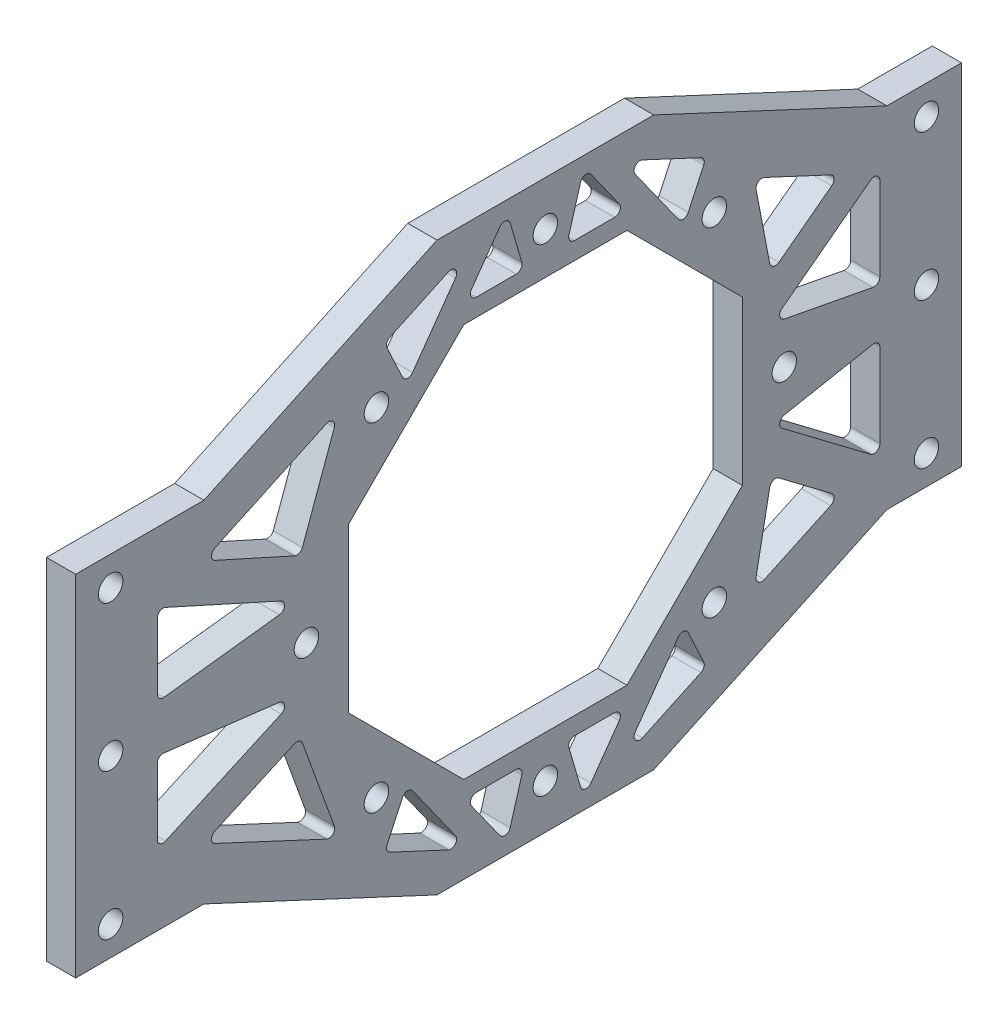
SolidWorks part; units mm, degrees
material "玻纤"
ref_plane "前视基准面" through (0, 0, 0) normal (0, 0, 1) x (1, 0, 0)
ref_plane "上视基准面" through (0, 0, 0) normal (0, 1, 0) x (1, 0, 0)
ref_plane "右视基准面" through (0, 0, 0) normal (1, 0, 0) x (0, 0, -1)
sketch "草图1" plane through (0, 0, 0) normal (1, 0, 0) x (0, 0, -1)
  line L0 (-74.6, 30) -> (-74.6, -30) construction
  line L1 (-78.6, -30) -> (78.6, -30)
  line L2 (-78.6, -30) -> (-78.6, 30)
  line L3 (-78.6, 30) -> (78.6, 30)
  line L4 (78.6, -30) -> (78.6, 30)
  line L5 (-78.6, -30) -> (78.6, 30) construction
  line L6 (-78.6, 30) -> (78.6, -30) construction
  line L7 (0, 0) -> (0, -30) construction
  line L8 (65.4, 30) -> (65.4, -30) construction
  line L9 (78.6, -30) -> (78.6, 30)
  circle A0 centre (-74.6, 0) radius 2.1
  circle A1 centre (-74.6, 25) radius 2.1
  circle A3 centre (-74.6, -25) radius 2.1
  circle A4 centre (65.4, -25) radius 2.1
  circle A6 centre (65.4, 25) radius 2.1
  circle A7 centre (65.4, 0) radius 2.1
  point P0 (0, 0)
  point P15 (-74.6, 0)
  dimension "D4" = 4.2
  dimension "D8" = 5
  dimension "D10" = 5
  dimension "D13" = 4.2
  dimension "D1" = 60
  dimension "D2" = 157.2
  dimension "D3" = 4
  dimension "D12" = 65.4
extrude "凸台-拉伸1" add sketch "草图1" along normal blind 5 contours L1 L4 L3 L2 A6 A4 A3 A1 A0 A7 region at (0, 0, -0.0409)
sketch "草图2" plane through (5, 0, 0) normal (1, 0, 0) x (0, 0, -1)
  line L0 (-58.6, 30) -> (-58.6, -30)
  line L1 (-78.6, 30) -> (78.6, 30) construction
  line L2 (-78.6, -30) -> (78.6, -30) construction
  line L3 (-58.6, -30) -> (-18.6, -48.6523)
  line L4 (-18.6, -48.6523) -> (18.6, -48.6523)
  line L5 (0, -48.6523) -> (0, 0)
  line L6 (-78.6, -30) -> (-78.6, 30) construction
  line L7 (58.6, -30) -> (18.6, -48.6523)
  line L8 (58.6, 30) -> (58.6, -30)
  line L9 (-58.6, 0) -> (58.6, 0) construction
  line L10 (58.6, 30) -> (18.6, 48.6523)
  line L11 (-18.6, 48.6523) -> (18.6, 48.6523)
  line L12 (-58.6, 30) -> (-18.6, 48.6523)
  circle A0 centre (0, 0) radius 41 construction
  circle A1 centre (-41, 0) radius 2.1
  circle A2 centre (-28.9914, 28.9914) radius 2.1
  circle A3 centre (0, 41) radius 2.1
  circle A4 centre (28.9914, 28.9914) radius 2.1
  circle A5 centre (41, 0) radius 2.1
  circle A6 centre (28.9914, -28.9914) radius 2.1
  circle A7 centre (0, -41) radius 2.1
  circle A8 centre (-28.9914, -28.9914) radius 2.1
  line M13 (-78.6, -30) -> (78.6, -30)
  line M15 (78.6, 30) -> (-78.6, 30)
  dimension "D1" = 82
  dimension "D5" = 4.2
  dimension "D2" = 20
  dimension "D3" = 25
  dimension "D4" = 40
  dimension "D6" = 8
extrude "凸台-拉伸2" add sketch "草图2" against normal blind 5 contours A4 L10 L11 L12 A2 A3 M15 | A8 L3 L4 L5 A7 M13 | A7 L5 L4 L7 A6 M13 region at (5, 37.7126, 0) region at (5, -37.7126, 21.1914) region at (5, -37.7126, -21.1914)
extrude "切除-拉伸1" cut sketch "草图2<3>" against normal blind 5 contours A2 M15 | A8 M13 | A6 M13 | A5 | A4 M15 | A1 region at (5, 28.6125, 28.9914) region at (5, -28.6125, 28.9914) region at (5, 28.6125, -28.9914) region at (5, -28.6125, -28.9914) region at (5, 0, -41)
sketch "草图2<3>" plane through (5, 0, 0) normal (1, 0, 0) x (0, 0, -1) same geometry as "草图2"
sketch "草图3" plane through (0, 0, 0) normal (-1, 0, 0) x (0, 0, 1)
  line L7 (-14, 33.799) -> (-33.799, 14)
  line L8 (-33.799, 14) -> (-33.799, -14)
  line L9 (-33.799, -14) -> (-14, -33.799)
  line L10 (-14, -33.799) -> (14, -33.799)
  line L11 (14, -33.799) -> (33.799, -14)
  line L12 (33.799, -14) -> (33.799, 14)
  line L13 (33.799, 14) -> (14, 33.799)
  line L14 (14, 33.799) -> (-14, 33.799)
  circle A0 centre (0, 0) radius 33.799 construction
  dimension "D1" = 28
extrude "切除-拉伸2" cut sketch "草图3" against normal blind 5
sketch "草图4" plane through (0, 0, 0) normal (-1, 0, 0) x (0, 0, 1)
  line L0 (-58.6, -30) -> (-78.6, -30) construction
  line L1 (-78.6, 30) -> (-71.4, 30)
  line L2 (-78.6, 30) -> (-78.6, -30)
  line L3 (-78.6, -30) -> (-71.4, -30)
  line L4 (-71.4, 30) -> (-71.4, -30)
  line L5 (-48.9578, 24.5658) -> (-37.5643, 29.8787)
  line L6 (-36.1597, 28.7835) -> (-38.4959, 16.6375)
  line L7 (-40.0801, 16.0281) -> (-49.1375, 22.8612)
  line L8 (-55.7977, 20.3699) -> (-40.5994, 8.9039)
  line L9 (-41.0145, 7.1233) -> (-56.2128, 4.2263)
  line L10 (-57.4, 5.2086) -> (-57.4, 19.5716)
  line L11 (-58.6, 30) -> (-18.6, 48.6523) construction
  line L12 (-33.799, 14) -> (-33.799, -14) construction
  line L16 (-11.8725, 36.799) -> (-5, 36.799)
  line L17 (-16.643, 42.9446) -> (-26.6924, 38.2585)
  line L18 (-27.1761, 36.9296) -> (-24.5153, 31.2234)
  line L19 (-22.794, 31.0665) -> (-15.4053, 41.4589)
  line L27 (-14, 33.799) -> (-33.799, 14) construction
  line L32 (-12.6875, 38.3784) -> (-7.815, 45.2318)
  line L33 (-6.04, 44.9325) -> (-4.04, 38.0791)
  line L34 (18.6, 48.6523) -> (-18.6, 48.6523) construction
  line L35 (14, 33.799) -> (-14, 33.799) construction
  line L36 (0, 33.799) -> (0, -33.799) construction
  line L37 (-14, -33.799) -> (14, -33.799) construction
  line L38 (-33.799, 0) -> (33.799, 0) construction
  line L39 (33.799, -14) -> (33.799, 14) construction
  line L40 (-12.6875, -38.3784) -> (-7.815, -45.2318)
  line L41 (-11.8725, -36.799) -> (-5, -36.799)
  line L42 (-6.04, -44.9325) -> (-4.04, -38.0791)
  line L43 (-27.1761, -36.9296) -> (-24.5153, -31.2234)
  line L44 (-16.643, -42.9446) -> (-26.6924, -38.2585)
  line L45 (-22.794, -31.0665) -> (-15.4053, -41.4589)
  line L46 (-36.1597, -28.7835) -> (-38.4959, -16.6375)
  line L47 (-48.9578, -24.5658) -> (-37.5643, -29.8787)
  line L48 (-40.0801, -16.0281) -> (-49.1375, -22.8612)
  line L49 (-41.0145, -7.1233) -> (-56.2128, -4.2263)
  line L50 (-55.7977, -20.3699) -> (-40.5994, -8.9039)
  line L51 (-57.4, -5.2086) -> (-57.4, -19.5716)
  line L52 (11.8725, -36.799) -> (5, -36.799)
  line L53 (6.04, -44.9325) -> (4.04, -38.0791)
  line L54 (12.6875, -38.3784) -> (7.815, -45.2318)
  line L55 (16.643, -42.9446) -> (26.6924, -38.2585)
  line L56 (22.794, -31.0665) -> (15.4053, -41.4589)
  line L57 (27.1761, -36.9296) -> (24.5153, -31.2234)
  line L64 (12.6875, 38.3784) -> (7.815, 45.2318)
  line L65 (11.8725, 36.799) -> (5, 36.799)
  line L66 (6.04, 44.9325) -> (4.04, 38.0791)
  line L67 (27.1761, 36.9296) -> (24.5153, 31.2234)
  line L68 (16.643, 42.9446) -> (26.6924, 38.2585)
  line L69 (22.794, 31.0665) -> (15.4053, 41.4589)
  line L76 (37.5709, 30.873) -> (56.7287, 21.9396)
  line L77 (56.7175, 20.1219) -> (43.0449, 13.9499)
  line L78 (41.6935, 14.52) -> (36.2084, 29.6254)
  line L79 (45.3384, 8.4022) -> (65.1886, 17.3629)
  line L80 (66.6, 16.4514) -> (66.6, 5.1262)
  line L81 (65.4817, 4.1332) -> (45.6316, 6.4978)
  line L82 (58.6, 30) -> (18.6, 48.6523) construction
  line L83 (78.6, 30) -> (58.6, 30) construction
  line L84 (66.6, -16.4514) -> (66.6, -5.1262)
  line L85 (45.3384, -8.4022) -> (65.1886, -17.3629)
  line L86 (65.4817, -4.1332) -> (45.6316, -6.4978)
  line L87 (56.7175, -20.1219) -> (43.0449, -13.9499)
  line L88 (37.5709, -30.873) -> (56.7287, -21.9396)
  line L89 (41.6935, -14.52) -> (36.2084, -29.6254)
  circle A0 centre (-65.4, 25) radius 2.1 construction
  circle A2 centre (-41, 0) radius 2.1 construction
  circle A3 centre (-28.9914, 28.9914) radius 2.1 construction
  circle A4 centre (-65.4, 0) radius 2.1 construction
  arc A5 (-55.7977, 20.3699) -> (-57.4, 19.5716) centre (-56.4, 19.5716) ccw
  arc A6 (-56.2128, 4.2263) -> (-57.4, 5.2086) centre (-56.4, 5.2086) cw
  arc A7 (-40.5994, 8.9039) -> (-41.0145, 7.1233) centre (-41.2017, 8.1056) cw
  arc A8 (-37.5643, 29.8787) -> (-36.1597, 28.7835) centre (-37.1417, 28.9724) cw
  arc A9 (-38.4959, 16.6375) -> (-40.0801, 16.0281) centre (-39.4779, 16.8264) cw
  arc A10 (-48.9578, 24.5658) -> (-49.1375, 22.8612) centre (-48.5352, 23.6595) ccw
  arc A17 (-16.643, 42.9446) -> (-15.4053, 41.4589) centre (-16.2203, 42.0383) cw
  arc A18 (-24.5153, 31.2234) -> (-22.794, 31.0665) centre (-23.609, 31.646) ccw
  arc A19 (-26.6924, 38.2585) -> (-27.1761, 36.9296) centre (-26.2698, 37.3522) ccw
  arc A20 (-5, 36.799) -> (-4.04, 38.0791) centre (-5, 37.799) ccw
  arc A21 (-11.8725, 36.799) -> (-12.6875, 38.3784) centre (-11.8725, 37.799) cw
  arc A22 (-7.815, 45.2318) -> (-6.04, 44.9325) centre (-7, 44.6523) cw
  circle A23 centre (0, 41) radius 2.1 construction
  arc A24 (-11.8725, -36.799) -> (-12.6875, -38.3784) centre (-11.8725, -37.799) ccw
  arc A25 (-5, -36.799) -> (-4.04, -38.0791) centre (-5, -37.799) cw
  arc A26 (-7.815, -45.2318) -> (-6.04, -44.9325) centre (-7, -44.6523) ccw
  arc A27 (-26.6924, -38.2585) -> (-27.1761, -36.9296) centre (-26.2698, -37.3522) cw
  arc A28 (-16.643, -42.9446) -> (-15.4053, -41.4589) centre (-16.2203, -42.0383) ccw
  arc A29 (-24.5153, -31.2234) -> (-22.794, -31.0665) centre (-23.609, -31.646) cw
  arc A30 (-37.5643, -29.8787) -> (-36.1597, -28.7835) centre (-37.1417, -28.9724) ccw
  arc A31 (-38.4959, -16.6375) -> (-40.0801, -16.0281) centre (-39.4779, -16.8264) ccw
  arc A32 (-48.9578, -24.5658) -> (-49.1375, -22.8612) centre (-48.5352, -23.6595) cw
  arc A33 (-40.5994, -8.9039) -> (-41.0145, -7.1233) centre (-41.2017, -8.1056) ccw
  arc A34 (-55.7977, -20.3699) -> (-57.4, -19.5716) centre (-56.4, -19.5716) cw
  arc A35 (-56.2128, -4.2263) -> (-57.4, -5.2086) centre (-56.4, -5.2086) ccw
  arc A36 (11.8725, -36.799) -> (12.6875, -38.3784) centre (11.8725, -37.799) cw
  arc A37 (5, -36.799) -> (4.04, -38.0791) centre (5, -37.799) ccw
  arc A38 (7.815, -45.2318) -> (6.04, -44.9325) centre (7, -44.6523) cw
  arc A39 (26.6924, -38.2585) -> (27.1761, -36.9296) centre (26.2698, -37.3522) ccw
  arc A40 (16.643, -42.9446) -> (15.4053, -41.4589) centre (16.2203, -42.0383) cw
  arc A41 (24.5153, -31.2234) -> (22.794, -31.0665) centre (23.609, -31.646) ccw
  arc A48 (11.8725, 36.799) -> (12.6875, 38.3784) centre (11.8725, 37.799) ccw
  arc A49 (5, 36.799) -> (4.04, 38.0791) centre (5, 37.799) cw
  arc A50 (7.815, 45.2318) -> (6.04, 44.9325) centre (7, 44.6523) ccw
  arc A51 (26.6924, 38.2585) -> (27.1761, 36.9296) centre (26.2698, 37.3522) cw
  arc A52 (16.643, 42.9446) -> (15.4053, 41.4589) centre (16.2203, 42.0383) ccw
  arc A53 (24.5153, 31.2234) -> (22.794, 31.0665) centre (23.609, 31.646) cw
  circle A60 centre (28.9914, 28.9914) radius 2.1 construction
  circle A61 centre (41, 0) radius 2.1 construction
  circle A62 centre (74.6, 0) radius 2.1 construction
  arc A63 (66.6, 5.1262) -> (65.4817, 4.1332) centre (65.6, 5.1262) cw
  arc A64 (45.3384, 8.4022) -> (45.6316, 6.4978) centre (45.7499, 7.4908) ccw
  arc A65 (65.1886, 17.3629) -> (66.6, 16.4514) centre (65.6, 16.4514) cw
  arc A66 (56.7287, 21.9396) -> (56.7175, 20.1219) centre (56.3061, 21.0333) cw
  arc A67 (43.0449, 13.9499) -> (41.6935, 14.52) centre (42.6335, 14.8613) cw
  arc A68 (37.5709, 30.873) -> (36.2084, 29.6254) centre (37.1483, 29.9667) ccw
  arc A69 (65.1886, -17.3629) -> (66.6, -16.4514) centre (65.6, -16.4514) ccw
  arc A70 (66.6, -5.1262) -> (65.4817, -4.1332) centre (65.6, -5.1262) ccw
  arc A71 (45.3384, -8.4022) -> (45.6316, -6.4978) centre (45.7499, -7.4908) cw
  arc A72 (56.7287, -21.9396) -> (56.7175, -20.1219) centre (56.3061, -21.0333) ccw
  arc A73 (43.0449, -13.9499) -> (41.6935, -14.52) centre (42.6335, -14.8613) ccw
  arc A74 (37.5709, -30.873) -> (36.2084, -29.6254) centre (37.1483, -29.9667) cw
  point P35 (-57.4, 4)
  point P38 (-38.799, 7.5456)
  point P43 (-38.799, 15.0615)
  point P84 (-13.2113, 44.5448)
  point P87 (-23.7893, 29.6665)
  point P173 (66.6, 4)
  point P176 (42.0617, 6.923)
  point P179 (66.6, 18)
  point P184 (42.0617, 13.506)
  dimension "D2" = 9
  dimension "D9" = 1
  dimension "D15" = 3
  dimension "D19" = 6
  dimension "D11" = 1
  dimension "D17" = 7
  dimension "D26" = 1
  dimension "D1" = 6
  dimension "D3" = 6
  dimension "D4" = 7
  dimension "D5" = 7
  dimension "D6" = 8
  dimension "D7" = 4
  dimension "D8" = 5
  dimension "D10" = 6
  dimension "D12" = 4
  dimension "D13" = 5
  dimension "D14" = 4
  dimension "D16" = 4
  dimension "D18" = 5
  dimension "D20" = 8.096
  dimension "D21" = 7
  dimension "D22" = 7
  dimension "D23" = 8
  dimension "D24" = 4
  dimension "D25" = 12
extrude "切除-拉伸3" cut sketch "草图4" against normal through all
sketch "草图5" plane through (0, 0, 0) normal (-1, 0, 0) x (0, 0, 1)
  line L1 (78.6, 30) -> (80.6, 30)
  line L2 (78.6, 30) -> (78.6, -30)
  line L3 (78.6, -30) -> (80.6, -30)
  line L4 (80.6, 30) -> (80.6, -30)
  dimension "D1" = 2
extrude "凸台-拉伸3" add sketch "草图5" against normal up to surface (5 mm away) up to face at (5, 0, 1.2)
